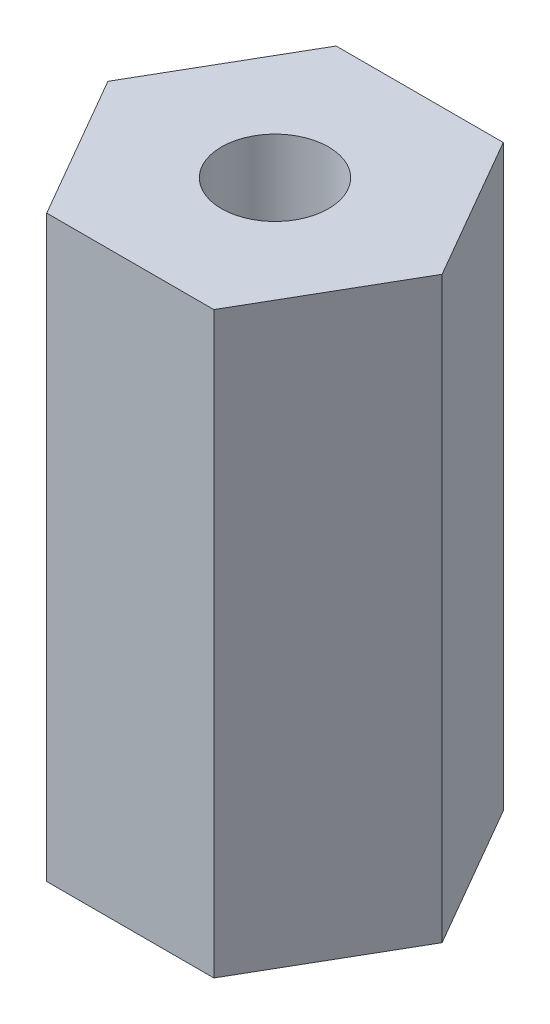
SolidWorks part; units mm, degrees
ref_plane "Front Plane" through (0, 0, 0) normal (0, 0, 1) x (1, 0, 0)
ref_plane "Top Plane" through (0, 0, 0) normal (0, 1, 0) x (1, 0, 0)
ref_plane "Right Plane" through (0, 0, 0) normal (1, 0, 0) x (0, 0, -1)
sketch "Sketch1" plane through (0, 0, 0) normal (0, 1, 0) x (1, 0, 0)
  line L2 (14.6647, 0) -> (7.3323, 12.7)
  line L3 (7.3323, 12.7) -> (-7.3323, 12.7)
  line L4 (-7.3323, 12.7) -> (-14.6647, 0)
  line L5 (-14.6647, 0) -> (-7.3323, -12.7)
  line L6 (-7.3323, -12.7) -> (7.3323, -12.7)
  line L7 (7.3323, -12.7) -> (14.6647, 0)
  circle A0 centre (0, 0) radius 12.7 construction
  dimension "D1" = 29.3294
extrude "Boss-Extrude1" add sketch "Sketch1" along normal blind 50.8
sketch "Sketch2" plane through (0, 0, 0) normal (0, -1, 0) x (1, 0, 0)
  circle A0 centre (0, 0) radius 4.699
  dimension "D1" = 9.398
extrude "Cut-Extrude1" cut sketch "Sketch2" against normal up to surface (50.8 mm away) up to face at (0, 50.8, 0)
